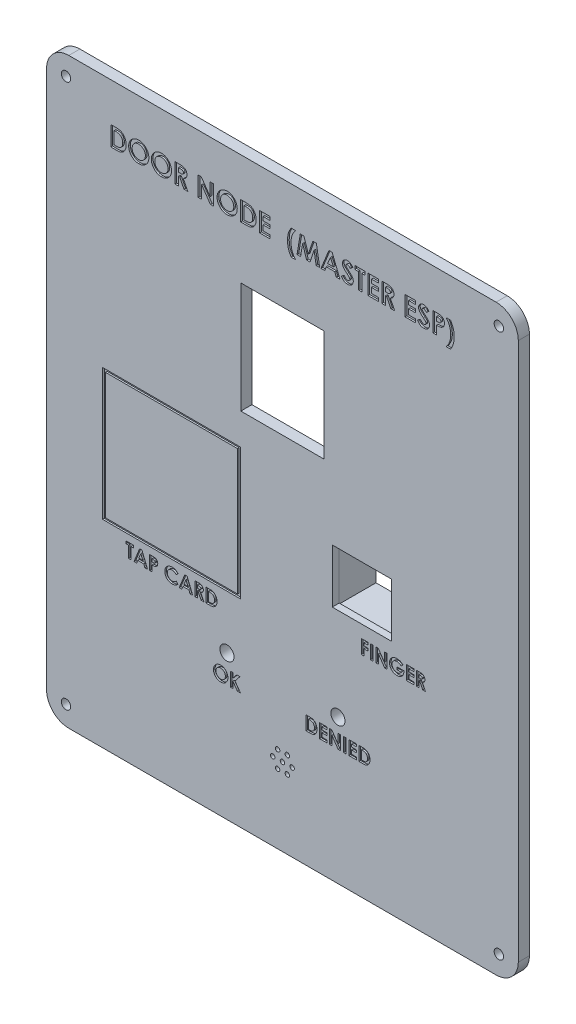
SolidWorks part; units mm, degrees
ref_plane "Front Plane" through (0, 0, 0) normal (0, 0, 1) x (1, 0, 0)
ref_plane "Top Plane" through (0, 0, 0) normal (0, 1, 0) x (1, 0, 0)
ref_plane "Right Plane" through (0, 0, 0) normal (1, 0, 0) x (0, 0, -1)
sketch "Sketch1" plane through (0, 0, 0) normal (0, 0, 1) x (1, 0, 0)
  line L0 (-77, 0) -> (77, 0)
  line L1 (85, 8) -> (85, 202)
  line L2 (77, 210) -> (-77, 210)
  line L3 (-85, 202) -> (-85, 8)
  arc A0 (-85, 8) -> (-77, 0) centre (-77, 8) ccw
  arc A1 (77, 0) -> (85, 8) centre (77, 8) ccw
  arc A2 (85, 202) -> (77, 210) centre (77, 202) ccw
  arc A3 (-77, 210) -> (-85, 202) centre (-77, 202) ccw
extrude "Panel" add sketch "Sketch1" along normal blind 4
ref_plane "P1_Front_4" through (0, 0, 4) normal (0, 0, 1) x (1, 0, 0)
sketch "Sketch2" plane through (0, 0, 0) normal (0, 0, 1) x (1, 0, 0)
  circle A0 centre (-78, 7) radius 1.7
  circle A1 centre (78, 7) radius 1.7
  circle A2 centre (-78, 203) radius 1.7
  circle A3 centre (78, 203) radius 1.7
extrude "Screw holes" cut sketch "Sketch2" along normal through all
ref_plane "P2_Front_-3" through (0, 0, -3) normal (0, 0, 1) x (1, 0, 0)
sketch "Sketch3" plane through (0, 0, -3) normal (0, 0, 1) x (1, 0, 0)
  line L1 (-15, 3.3) -> (15, 3.3)
  line L2 (-15, 3.3) -> (-15, 5.3)
  line L3 (-15, 5.3) -> (15, 5.3)
  line L4 (15, 3.3) -> (15, 5.3)
  line L6 (-15, 204.7) -> (15, 204.7)
  line L7 (-15, 204.7) -> (-15, 206.7)
  line L8 (-15, 206.7) -> (15, 206.7)
  line L9 (15, 204.7) -> (15, 206.7)
  line L11 (-81.7, 90) -> (-79.7, 90)
  line L12 (-81.7, 90) -> (-81.7, 120)
  line L13 (-81.7, 120) -> (-79.7, 120)
  line L14 (-79.7, 90) -> (-79.7, 120)
  line L16 (79.7, 90) -> (81.7, 90)
  line L17 (79.7, 90) -> (79.7, 120)
  line L18 (79.7, 120) -> (81.7, 120)
  line L19 (81.7, 90) -> (81.7, 120)
extrude "Locating tabs" add sketch "Sketch3" along normal blind 3
sketch "Sketch4" plane through (0, 0, 0) normal (0, 0, 1) x (1, 0, 0)
  line L1 (-15, 130) -> (15, 130)
  line L2 (-15, 130) -> (-15, 170)
  line L3 (-15, 170) -> (15, 170)
  line L4 (15, 130) -> (15, 170)
  line L5 (-15, 130) -> (15, 170) construction
  line L6 (-15, 170) -> (15, 130) construction
  point P0 (0, 150)
extrude "TFT window" cut sketch "Sketch4" along normal through all
ref_plane "P3_Front_-2.4" through (0, 0, -2.4) normal (0, 0, 1) x (1, 0, 0)
sketch "Sketch5" plane through (0, 0, -2.4) normal (0, 0, 1) x (1, 0, 0)
  circle A0 centre (-14.25, 124) radius 2.1
  circle A1 centre (-14.25, 176) radius 2.1
  circle A2 centre (14.25, 124) radius 2.1
  circle A3 centre (14.25, 176) radius 2.1
extrude "TFT bosses" add sketch "Sketch5" along normal blind 2.4
ref_plane "P4_Front_-2.4" through (0, 0, -2.4) normal (0, 0, 1) x (1, 0, 0)
sketch "Sketch6" plane through (0, 0, -2.4) normal (0, 0, 1) x (1, 0, 0)
  circle A0 centre (-14.25, 124) radius 1.1
  circle A1 centre (-14.25, 176) radius 1.1
  circle A2 centre (14.25, 124) radius 1.1
  circle A3 centre (14.25, 176) radius 1.1
extrude "TFT pilot holes" cut sketch "Sketch6" along normal blind 4
sketch "Sketch7" plane through (0, 0, 0) normal (0, 0, 1) x (1, 0, 0)
  line L1 (-61.8, 74.3) -> (-18.2, 74.3)
  line L2 (-61.8, 74.3) -> (-61.8, 115.7)
  line L3 (-61.8, 115.7) -> (-18.2, 115.7)
  line L4 (-18.2, 74.3) -> (-18.2, 115.7)
  line L5 (-61.8, 74.3) -> (-18.2, 115.7) construction
  line L6 (-61.8, 115.7) -> (-18.2, 74.3) construction
  circle A0 centre (-53.9, 82.4) radius 3
  circle A1 centre (-53.9, 107.6) radius 3
  circle A2 centre (-26.1, 82.4) radius 3
  circle A3 centre (-26.1, 107.6) radius 3
  point P0 (-40, 95)
extrude "NFC pocket" cut sketch "Sketch7" along normal blind 2.5
sketch "Sketch8" plane through (0, 0, 0) normal (0, 0, 1) x (1, 0, 0)
  circle A0 centre (-53.9, 82.4) radius 1.1
  circle A1 centre (-53.9, 107.6) radius 1.1
  circle A2 centre (-26.1, 82.4) radius 1.1
  circle A3 centre (-26.1, 107.6) radius 1.1
extrude "NFC pilot holes" cut sketch "Sketch8" along normal blind 3
sketch "Sketch9" plane through (0, 0, 4) normal (0, 0, 1) x (1, 0, 0)
  line L1 (-64.8, 71.3) -> (-15.2, 71.3)
  line L2 (-64.8, 71.3) -> (-64.8, 118.7)
  line L3 (-64.8, 118.7) -> (-15.2, 118.7)
  line L4 (-15.2, 71.3) -> (-15.2, 118.7)
  line L5 (-64.8, 71.3) -> (-15.2, 118.7) construction
  line L6 (-64.8, 118.7) -> (-15.2, 71.3) construction
  point P0 (-40, 95)
extrude "NFC tap outline recess" cut sketch "Sketch9" against normal blind 0.6
ref_plane "P5_Front_3.4" through (0, 0, 3.4) normal (0, 0, 1) x (1, 0, 0)
sketch "Sketch10" plane through (0, 0, 3.4) normal (0, 0, 1) x (1, 0, 0)
  line L1 (-63.8, 72.3) -> (-16.2, 72.3)
  line L2 (-63.8, 72.3) -> (-63.8, 117.7)
  line L3 (-63.8, 117.7) -> (-16.2, 117.7)
  line L4 (-16.2, 72.3) -> (-16.2, 117.7)
  line L5 (-63.8, 72.3) -> (-16.2, 117.7) construction
  line L6 (-63.8, 117.7) -> (-16.2, 72.3) construction
  point P0 (-40, 95)
extrude "NFC tap outline fill" add sketch "Sketch10" along normal blind 0.6
sketch "Sketch11" plane through (0, 0, 0) normal (0, 0, 1) x (1, 0, 0)
  line L1 (17.7, 84.75) -> (62.3, 84.75)
  line L2 (17.7, 84.75) -> (17.7, 105.25)
  line L3 (17.7, 105.25) -> (62.3, 105.25)
  line L4 (62.3, 84.75) -> (62.3, 105.25)
  line L5 (17.7, 84.75) -> (62.3, 105.25) construction
  line L6 (17.7, 105.25) -> (62.3, 84.75) construction
  point P0 (40, 95)
extrude "Fingerprint pocket" cut sketch "Sketch11" along normal blind 1.5
sketch "Sketch12" plane through (0, 0, 0) normal (0, 0, 1) x (1, 0, 0)
  line L1 (17.95, 85.3) -> (39.35, 85.3)
  line L2 (17.95, 85.3) -> (17.95, 104.7)
  line L3 (17.95, 104.7) -> (39.35, 104.7)
  line L4 (39.35, 85.3) -> (39.35, 104.7)
  line L5 (17.95, 85.3) -> (39.35, 104.7) construction
  line L6 (17.95, 104.7) -> (39.35, 85.3) construction
  point P0 (28.65, 95)
extrude "Fingerprint aperture" cut sketch "Sketch12" along normal through all
ref_plane "P6_Front_-12" through (0, 0, -12) normal (0, 0, 1) x (1, 0, 0)
sketch "Sketch13" plane through (0, 0, -12) normal (0, 0, 1) x (1, 0, 0)
  line L1 (15.7, 105.25) -> (62.3, 105.25)
  line L2 (15.7, 105.25) -> (15.7, 107.25)
  line L3 (15.7, 107.25) -> (62.3, 107.25)
  line L4 (62.3, 105.25) -> (62.3, 107.25)
  line L6 (15.7, 82.75) -> (62.3, 82.75)
  line L7 (15.7, 82.75) -> (15.7, 84.75)
  line L8 (15.7, 84.75) -> (62.3, 84.75)
  line L9 (62.3, 82.75) -> (62.3, 84.75)
extrude "Fingerprint cradle sides" add sketch "Sketch13" along normal blind 12
ref_plane "P7_Front_-12" through (0, 0, -12) normal (0, 0, 1) x (1, 0, 0)
sketch "Sketch14" plane through (0, 0, -12) normal (0, 0, 1) x (1, 0, 0)
  line L1 (15.7, 84.75) -> (17.7, 84.75)
  line L2 (15.7, 84.75) -> (15.7, 105.25)
  line L3 (15.7, 105.25) -> (17.7, 105.25)
  line L4 (17.7, 84.75) -> (17.7, 105.25)
extrude "Fingerprint cradle end" add sketch "Sketch14" along normal blind 12
ref_plane "P8_Top_108.25" through (0, 108.25, 0) normal (0, 1, 0) x (1, 0, 0)
sketch "Sketch15" plane through (0, 108.25, 0) normal (0, 1, 0) x (1, 0, 0)
  line L1 (28, 8) -> (32, 8)
  line L2 (28, 8) -> (28, 10.5)
  line L3 (28, 10.5) -> (32, 10.5)
  line L4 (32, 8) -> (32, 10.5)
  line L5 (28, 8) -> (32, 10.5) construction
  line L6 (28, 10.5) -> (32, 8) construction
  line L7 (48, 8) -> (52, 8)
  line L8 (48, 8) -> (48, 10.5)
  line L9 (48, 10.5) -> (52, 10.5)
  line L10 (52, 8) -> (52, 10.5)
  line L11 (48, 8) -> (52, 10.5) construction
  line L12 (48, 10.5) -> (52, 8) construction
  point P0 (30, 9.25)
  point P5 (50, 9.25)
extrude "Fingerprint tie slots" cut sketch "Sketch15" against normal through all
sketch "Sketch16" plane through (0, 0, 0) normal (0, 0, 1) x (1, 0, 0)
  circle A0 centre (-20, 52) radius 2.55
  circle A1 centre (20, 52) radius 2.55
extrude "LED holes" cut sketch "Sketch16" along normal through all
sketch "Sketch17" plane through (0, 0, 0) normal (0, 0, 1) x (1, 0, 0)
  circle A0 centre (0, 28) radius 0.8
  circle A1 centre (3.5, 28) radius 0.8
  circle A2 centre (1.75, 31.0311) radius 0.8
  circle A3 centre (-1.75, 31.0311) radius 0.8
  circle A4 centre (-3.5, 28) radius 0.8
  circle A5 centre (-1.75, 24.9689) radius 0.8
  circle A6 centre (1.75, 24.9689) radius 0.8
extrude "Buzzer sound holes" cut sketch "Sketch17" along normal through all
ref_plane "P9_Front_-7" through (0, 0, -7) normal (0, 0, 1) x (1, 0, 0)
sketch "Sketch18" plane through (0, 0, -7) normal (0, 0, 1) x (1, 0, 0)
  circle A0 centre (0, 28) radius 7.85
  circle A1 centre (0, 28) radius 6.25
extrude "Buzzer cradle" add sketch "Sketch18" along normal blind 7
sketch "Sketch19" plane through (0, 0, 4) normal (0, 0, 1) x (1, 0, 0)
  text T0 "DOOR NODE  (MASTER ESP)" font "Century Gothic" height 7
  text T1 "TAP CARD" font "Century Gothic" height 5
  text T2 "FINGER" font "Century Gothic" height 5
  text T3 "OK" font "Century Gothic" height 5
  text T4 "DENIED" font "Century Gothic" height 5
extrude "Labels (engraved)" cut sketch "Sketch19" against normal blind 0.6
